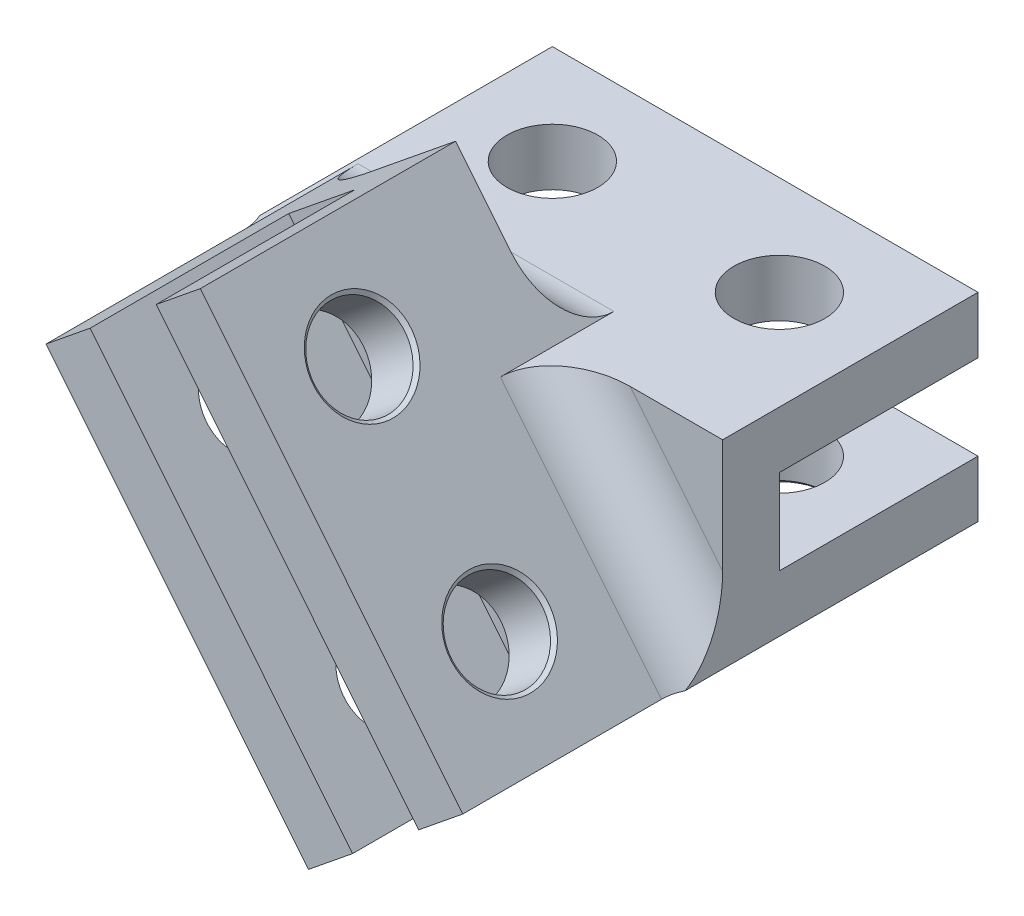
SolidWorks part; units mm, degrees
ref_plane "Front Plane" through (0, 0, 0) normal (0, 0, 1) x (1, 0, 0)
ref_plane "Top Plane" through (0, 0, 0) normal (0, 1, 0) x (1, 0, 0)
ref_plane "Right Plane" through (0, 0, 0) normal (1, 0, 0) x (0, 0, -1)
sketch "Sketch1" plane through (0, 0, 0) normal (0, 0, 1) x (1, 0, 0)
  line L0 (58.5, 3) -> (43.5, 3)
  line L2 (36, 1.5) -> (66, 1.5) construction
  line L5 (58.5, 3) -> (58.5, 5)
  line L6 (58.5, 5) -> (43.5, 5)
  line L7 (43.5, 5) -> (43.5, 3)
  line L8 (36, 3) -> (66, 3) construction
  line L9 (43.5, -2) -> (43.5, 0)
  line L10 (58.5, -2) -> (43.5, -2)
  line L11 (58.5, 0) -> (58.5, -2)
  line L12 (58.5, 0) -> (43.5, 0)
  point P5 (51, 3)
  point P15 (51, 3)
  point P20 (51, 0)
  dimension "D1" = 2
  dimension "D2" = 15
extrude "Boss-Extrude1" add sketch "Sketch1" against normal blind 7
sketch "Sketch2" plane through (0, 0, 0) normal (0, 0, 1) x (1, 0, 0)
  line L0 (43.5, -2) -> (58.5, -2) construction
  line L1 (58.5, 5) -> (43.5, 5) construction
  line L2 (43.5, -2) -> (58.5, -2)
  line L3 (58.5, 5) -> (43.5, 5)
  line L4 (43.5, -2) -> (43.5, 5)
  line L5 (58.5, -2) -> (58.5, 5)
extrude "Boss-Extrude2" add sketch "Sketch2" along normal blind 2
sketch "Sketch3" plane through (0, 0, 2) normal (0, 0, 1) x (1, 0, 0)
  line L0 (51, 5) -> (51, -2) construction
  line L1 (58.5, 5) -> (43.5, 5) construction
  line L2 (43.5, -2) -> (58.5, -2) construction
  line L3 (43.5, 1.5) -> (58.5, 1.5) construction
  line L4 (43.5, 5) -> (43.5, -2) construction
  line L5 (58.5, -2) -> (58.5, 5) construction
  line L6 (52.1651, 2.4448) -> (49.8349, 0.5552) construction
  line L7 (10.2298, 14.4655) -> (57.6089, 52.8871) construction
  line L8 (10.2298, 14.4655) -> (57.6089, 52.8871)
  line L9 (54.461, -5.1493) -> (45.2089, 6.2597)
  line L10 (53.8383, -2) -> (48.1617, 5) construction
  line L11 (54.461, -5.1493) -> (52.9076, -6.409)
  line L12 (52.9076, -6.409) -> (43.6555, 5)
  line L13 (43.6555, 5) -> (45.2089, 6.2597)
  line L14 (49.0924, 9.409) -> (47.539, 8.1493)
  line L15 (56.7911, -3.2597) -> (47.539, 8.1493)
  line L16 (58.3445, -2) -> (49.0924, 9.409)
  line L17 (56.7911, -3.2597) -> (58.3445, -2)
  point P15 (51, 1.5)
  point P21 (49.8349, 0.5552)
  point P23 (51, 1.5)
  line M9 (43.5, -2) -> (58.5, -2)
  line M11 (58.5, 5) -> (43.5, 5)
  dimension "D1" = 3
  dimension "D2" = 2
extrude "Boss-Extrude3" add sketch "Sketch3" along normal blind 9 contours L12 L9 M9 M11 | L12 L11 L9 M9 | L16 L15 M9 M11 | L16 L14 L15 M11 | L13 L9 M11 | L15 L17 M9 region at (52.0946, -3.9071, 2) region at (47.7813, 1.5, 2) region at (45.0316, 5.4199, 2) region at (56.9684, -2.4199, 2) region at (54.2187, 1.5, 2) region at (49.9054, 6.9071, 2)
sketch "Sketch4" plane through (0, 0, 2) normal (0, 0, 1) x (1, 0, 0)
  line L0 (43.6555, 5) -> (52.9076, -6.409)
  line L1 (52.9076, -6.409) -> (58.3445, -2)
  line L2 (58.3445, -2) -> (49.0924, 9.409)
  line L3 (49.0924, 9.409) -> (43.6555, 5)
extrude "Boss-Extrude4" add sketch "Sketch4" along normal blind 2
hole_wizard "M3 Clearance Hole1" positions "Sketch7" profile "Sketch6" hole size "M3" standard "ANSI Metric" end condition through all
sketch "Sketch7" plane through (34.2192, 27.7498, 0) normal (0.7767, 0.6299, 0) x (0, 0, -1)
  line L0 (-7.5, -23.6134) -> (-7.5, -38.3024) construction
  line L1 (-11, -23.6134) -> (-2, -23.6134) construction
  line L2 (-11, -38.3024) -> (-2, -38.3024) construction
  line L4 (-11, -38.3024) -> (-11, -23.6134) construction
  line L5 (-11, -30.9579) -> (-2, -30.9579) construction
  line L6 (-2, -38.3024) -> (-2, -29.29) construction
  point P16 (-7.5, -27.1134)
  point P20 (-7.5, -34.8024)
  dimension "D1" = 3.5
  dimension "D2" = 3.5
sketch "Sketch6" plane through (56.14, 0.7185, 7.5) normal (0, 0, 1) x (-0.6299, 0.7767, 0)
  line L0 (0, 0) -> (0, 14.3069)
  line L1 (0, 14.3069) -> (1.6, 14.3069)
  line L2 (1.6, 14.3069) -> (1.6, 0.125)
  line L3 (1.6, 0.125) -> (1.725, 0)
  line L5 (1.725, 0) -> (0, 0)
  line L6 (-1.6, 0.125) -> (-1.725, 0) construction
  line L11 (0, -6.35) -> (0, 107.95) construction
  dimension "Thru Hole Dia." = 3.2
  dimension "Thru Hole Depth" = 14.3069
  dimension "Near C'Sink Dia." = 3.45
  dimension "Near C'Sink Angle" = 90
hole_wizard "M3 Clearance Hole2" positions "Sketch10" profile "Sketch11" hole size "M3" standard "ANSI Metric" end condition through all
sketch "Sketch10" plane through (0, -2, 0) normal (0, -1, 0) x (-1, 0, 0)
  line L0 (-58.5, 3.5) -> (-43.5, 3.5) construction
  line L1 (-58.5, -2) -> (-58.5, 7) construction
  line L2 (-43.5, -2) -> (-43.5, 7) construction
  line L4 (-51, 7) -> (-51, -2) construction
  line L5 (-43.5, 7) -> (-58.5, 7) construction
  line L6 (-52.9076, -2) -> (-49.3321, -2) construction
  point P16 (-55, 3.5)
  point P19 (-47, 3.5)
  dimension "D1" = 3.5
  dimension "D2" = 3.5
sketch "Sketch11" plane through (47, -2, -3.5) normal (1, 0, 0) x (0, 0, -1)
  line L0 (0, 0) -> (0, 11.409)
  line L1 (0, 11.409) -> (1.6, 11.409)
  line L2 (1.6, 11.409) -> (1.6, 0.125)
  line L3 (1.6, 0.125) -> (1.725, 0)
  line L5 (1.725, 0) -> (0, 0)
  line L6 (-1.6, 0.125) -> (-1.725, 0) construction
  line L11 (0, -6.35) -> (0, 107.95) construction
  dimension "Thru Hole Dia." = 3.2
  dimension "Thru Hole Depth" = 11.409
  dimension "Near C'Sink Dia." = 3.45
  dimension "Near C'Sink Angle" = 90
fillet "Fillet2" radius 2 2 edges at (53.8383, -2, 2) (48.1617, 5, 2)
fillet "Fillet3" radius 2 2 edges at (46.4938, 1.5, 2) (55.5062, 1.5, 2)
